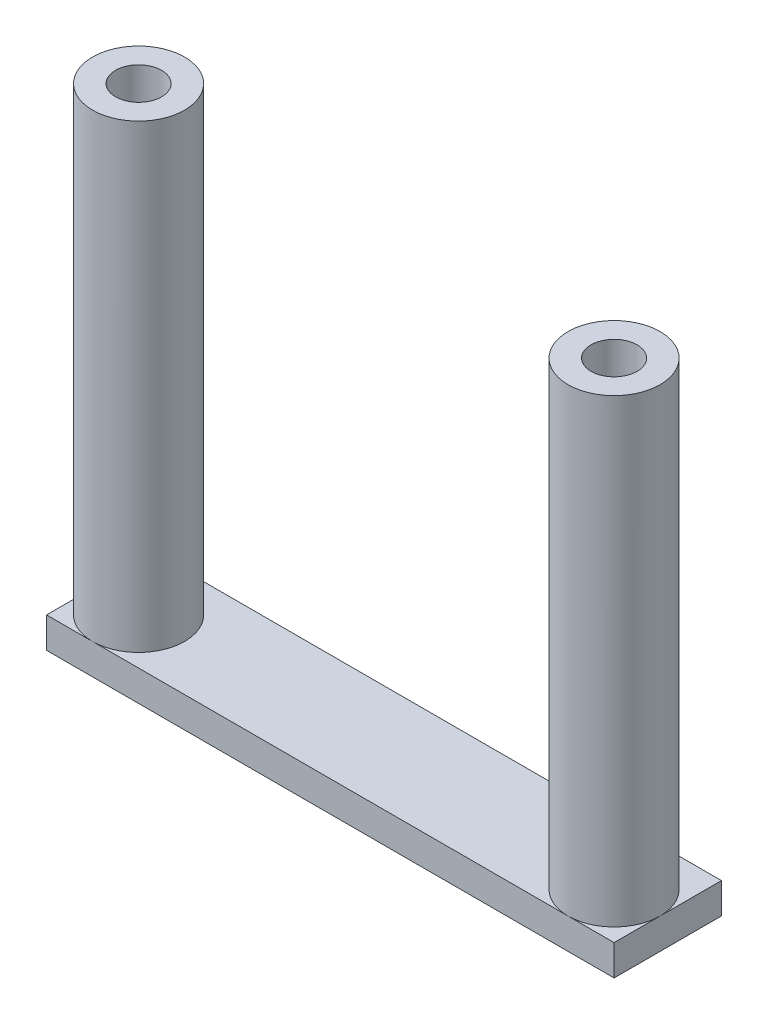
SolidWorks part; units mm, degrees
ref_plane "Front Plane" through (0, 0, 0) normal (0, 0, 1) x (1, 0, 0)
ref_plane "Top Plane" through (0, 0, 0) normal (0, 1, 0) x (1, 0, 0)
ref_plane "Right Plane" through (0, 0, 0) normal (1, 0, 0) x (0, 0, -1)
sketch "Sketch1" plane through (0, 0, 0) normal (0, 1, 0) x (1, 0, 0)
  line L0 (-3, 28) -> (34, 28)
  line L1 (0, 0) -> (31, 0)
  line L2 (0, 0) -> (0, 25)
  line L3 (0, 25) -> (31, 25)
  line L4 (31, 0) -> (31, 25)
  line L5 (34, -3) -> (34, 28)
  line L6 (-3, -3) -> (34, -3)
  line L7 (-3, -3) -> (-3, 28)
  circle A0 centre (0, 25) radius 1.5
  circle A1 centre (31, 25) radius 1.5
  circle A2 centre (31, 0) radius 1.5
  circle A3 centre (0, 0) radius 1.5
  dimension "D3" = 3
  dimension "D1" = 25
  dimension "D2" = 31
  dimension "D4" = 3
extrude "Boss-Extrude1" add sketch "Sketch1" along normal blind 2 contours L7 L6 L5 L0 A3 L2 A0 L3 A1 L4 A2 L1 | A3 L1 A2 L4 A1 L3 A0 L2 region at (15.5, 0, -27.5173) region at (15.5, 0, -12.5)
sketch "Sketch2" plane through (0, 2, 0) normal (0, 1, 0) x (1, 0, 0)
  circle A0 centre (31, 25) radius 1.5 construction
  circle A1 centre (31, 0) radius 1.5 construction
  circle A2 centre (0, 0) radius 1.5 construction
  circle A3 centre (0, 25) radius 1.5 construction
  circle A4 centre (31, 25) radius 1.5
  circle A5 centre (31, 0) radius 1.5
  circle A6 centre (0, 0) radius 1.5
  circle A7 centre (0, 25) radius 1.5
  circle A8 centre (0, 25) radius 3
  circle A9 centre (31, 25) radius 3
  circle A10 centre (31, 0) radius 3
  circle A11 centre (0, 0) radius 3
  dimension "D1" = 1.5
extrude "Boss-Extrude2" add sketch "Sketch2" along normal blind 30
sketch "Sketch3" plane through (0, 0, 0) normal (0, -1, 0) x (1, 0, 0)
  line L0 (-3, 3) -> (-3, -28) construction
  line L1 (34, -4) -> (-3, -4)
  line L2 (34, -4) -> (34, -28)
  line L3 (34, -28) -> (-3, -28)
  line L4 (-3, -4) -> (-3, -28)
  line L5 (-3, -28) -> (34, -28) construction
  line L6 (-3, 3) -> (34, 3) construction
  dimension "D1" = 0
  dimension "D2" = 0
  dimension "D3" = 7
extrude "Cut-Extrude1" cut sketch "Sketch3" against normal through all
